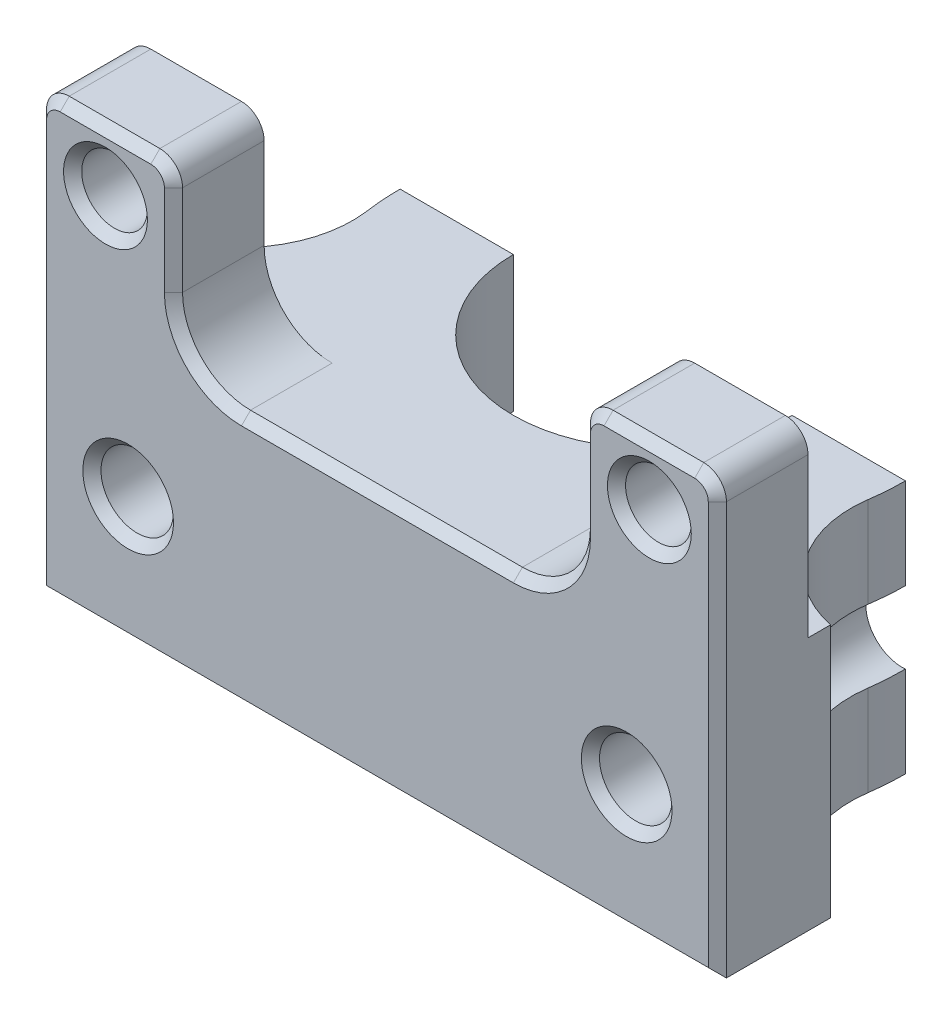
SolidWorks part; units mm, degrees
ref_plane "前视基准面" through (0, 0, 0) normal (0, 0, 1) x (1, 0, 0)
ref_plane "上视基准面" through (0, 0, 0) normal (0, 1, 0) x (1, 0, 0)
ref_plane "右视基准面" through (0, 0, 0) normal (1, 0, 0) x (0, 0, -1)
other "Configuration Table"
sketch "草图1" plane through (0, 0, 0) normal (0, 1, 0) x (1, 0, 0)
  line L0 (-11.15, 0) -> (-8.15, 0)
  line L1 (8.15, 0) -> (11.15, 0)
  arc A0 (-8.15, 0) -> (8.15, 0) centre (0, 0) ccw
  arc A1 (-11.15, 0) -> (11.15, 0) centre (0, 0) ccw
  circle A3 centre (0, 0) radius 11.15 construction
  circle A4 centre (0, 0) radius 8.15 construction
  point P4 (7.7939, 2.3828)
  point P7 (11.15, 0)
  dimension "D1" = 16.3
  dimension "D2" = 3
extrude "凸台-拉伸1" add sketch "草图1" along normal blind 5.2
sketch "草图2" plane through (0, 5.2, 0) normal (0, 1, 0) x (1, 0, 0)
  line L0 (-11.15, 0) -> (-6.15, 0)
  line L1 (6.15, 0) -> (11.15, 0)
  arc A0 (-11.15, 0) -> (11.15, 0) centre (0, 0) ccw
  arc A1 (-6.15, 0) -> (6.15, 0) centre (0, 0) ccw
  dimension "D1" = 12.3
extrude "凸台-拉伸2" add sketch "草图2" along normal blind 6
sketch "草图3" plane through (0, 11.2, 0) normal (0, 1, 0) x (1, 0, 0)
  line L0 (3.9115, -7.15) -> (15, -7.15)
  line L1 (-15, -7.15) -> (-3.9115, -7.15)
  line L2 (-15, -7.15) -> (-15, -11.15)
  line L3 (-15, -11.15) -> (15, -11.15)
  line L4 (15, -7.15) -> (15, -11.15)
  arc A0 (-11.15, 0) -> (11.15, 0) centre (0, 0) ccw construction
  arc A1 (-3.9115, -7.15) -> (3.9115, -7.15) centre (0, 0) ccw
  point P7 (0, -11.15)
  dimension "D1" = 11.15
  dimension "D2" = 30
  dimension "D3" = 0
  dimension "D4" = 4
extrude "凸台-拉伸3" add sketch "草图3" against normal up to surface (11.2 mm away) up to face at (0, 0, 4.825)
fillet "圆角1" radius 5 2 edges at (-8.5557, 5.6, 7.15) (8.5557, 5.6, 7.15)
sketch "草图4" plane through (0, 0, 11.15) normal (0, 0, 1) x (1, 0, 0)
  line L0 (-15, 0) -> (-15, 11.2) construction
  line L1 (15, 0) -> (15, 11.2) construction
  line L2 (-15, 11.2) -> (15, 11.2) construction
  circle A0 centre (-11, 5.6) radius 1.6
  circle A1 centre (11, 5.6) radius 1.6
  point P6 (-15, 5.6)
  point P9 (15, 5.6)
  point P12 (0, 11.2)
  dimension "D1" = 3.2
  dimension "D2" = 3.2
  dimension "D3" = 0
  dimension "D4" = 0
  dimension "D5" = 11
  dimension "D6" = 11
extrude "切除-拉伸1" cut sketch "草图4" against normal through all
sketch "草图7" plane through (0, 11.2, 0) normal (0, 1, 0) x (1, 0, 0)
  line L1 (-15, -11.15) -> (-9, -11.15)
  line L2 (-15, -11.15) -> (-15, -8.15)
  line L3 (-15, -8.15) -> (-9, -8.15)
  line L4 (-9, -11.15) -> (-9, -8.15)
  line L5 (15, -11.15) -> (9, -11.15)
  line L6 (15, -11.15) -> (15, -8.15)
  line L7 (15, -8.15) -> (9, -8.15)
  line L8 (9, -11.15) -> (9, -8.15)
  dimension "D1" = 3
  dimension "D2" = 3
  dimension "D3" = 6
  dimension "D4" = 6
extrude "凸台-拉伸5" add sketch "草图7" along normal blind 8
sketch "草图8" plane through (0, 0, 11.15) normal (0, 0, 1) x (1, 0, 0)
  line L0 (-15, 0) -> (-15, 19.2) construction
  circle A0 centre (-12, 16.6) radius 1.45
  circle A1 centre (12, 16.6) radius 1.45
  circle A2 centre (-11, 5.6) radius 1.6 construction
  circle A3 centre (11, 5.6) radius 1.6 construction
  dimension "D1" = 2.9
  dimension "D2" = 2.9
  dimension "D3" = 24
  dimension "D4" = 11
  dimension "D5" = 11
  dimension "D6" = 3
extrude "切除-拉伸3" cut sketch "草图8" against normal blind 8
sketch "草图9" plane through (0, 0, 11.15) normal (0, 0, 1) x (1, 0, 0)
  line L16 (-15, 19.2) -> (-15, 0)
  line L17 (-15, 0) -> (15, 0)
  line L18 (15, 0) -> (15, 19.2)
  line L19 (15, 19.2) -> (9, 19.2)
  line L20 (9, 19.2) -> (9, 11.2)
  line L21 (9, 11.2) -> (-9, 11.2)
  line L22 (-9, 11.2) -> (-9, 19.2)
  line L23 (-9, 19.2) -> (-15, 19.2)
  line L24 (-15, 19.2) -> (-15, 0)
  line L25 (-15, 0) -> (15, 0)
  line L26 (15, 0) -> (15, 19.2)
  line L27 (15, 19.2) -> (9, 19.2)
  line L28 (9, 19.2) -> (9, 11.2)
  line L29 (9, 11.2) -> (-9, 11.2)
  line L30 (-9, 11.2) -> (-9, 19.2)
  line L31 (-9, 19.2) -> (-15, 19.2)
  circle A0 centre (-12, 16.6) radius 1.45
  circle A1 centre (-11, 5.6) radius 1.6
  circle A2 centre (11, 5.6) radius 1.6
  circle A3 centre (12, 16.6) radius 1.45
  dimension "D1" = 0
extrude "凸台-拉伸6" add sketch "草图9" along normal blind 1
fillet "圆角2" radius 3 2 edges at (9, 11.2, 10.15) (-9, 11.2, 10.15)
fillet "圆角3" radius 1 4 edges at (15, 19.2, 10.15) (9, 19.2, 10.15) (-9, 19.2, 10.15) (-15, 19.2, 10.15)
chamfer "倒角1" distance 0.4 angle 45 18 edges at (13.45, 16.6, 12.15) (-9.4, 5.6, 12.15) (0, 0, 12.15) (-15, 9.1, 12.15) (-14.7071, 18.9071, 12.15) (-12, 19.2, 12.15) (-9.2929, 18.9071, 12.15) (-9, 16.2, 12.15) (-8.1213, 12.0787, 12.15) (0, 11.2, 12.15) (8.1213, 12.0787, 12.15) (9, 16.2, 12.15) (9.2929, 18.9071, 12.15) (12, 19.2, 12.15) (14.7071, 18.9071, 12.15) (15, 9.1, 12.15) (-10.55, 16.6, 12.15) (12.6, 5.6, 12.15)
equation "\"D1@草图3\"=22.3/2"
equation "\"D5@草图8\"=\"D4@草图8\""
